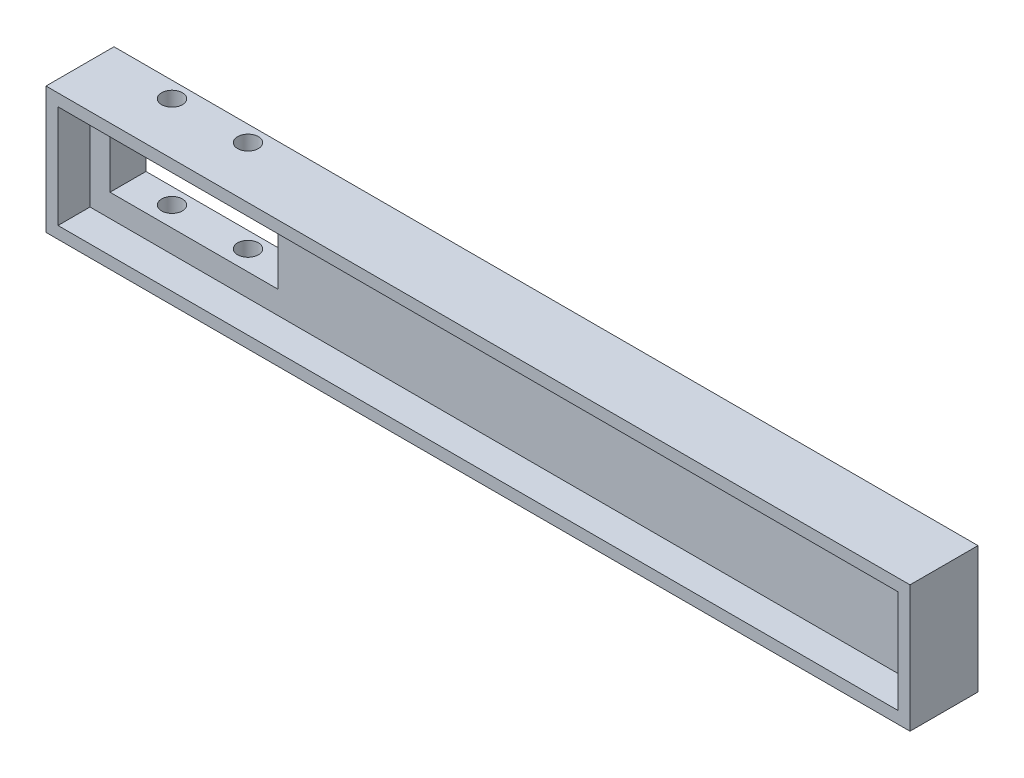
SolidWorks part; units mm, degrees
ref_plane "Plano frontal" through (0, 0, 0) normal (0, 0, 1) x (1, 0, 0)
ref_plane "Plano superior" through (0, 0, 0) normal (0, 1, 0) x (1, 0, 0)
ref_plane "Plano direito" through (0, 0, 0) normal (1, 0, 0) x (0, 0, -1)
sketch "Esboço1" plane through (0, 0, 0) normal (0, 0, 1) x (1, 0, 0)
  line L0 (-81, 8.8884) -> (-81, 14.3911)
  line L1 (0.5, 16.8911) -> (-96.5, 16.8911)
  line L2 (0.5, 16.8911) -> (0.5, 4.0411)
  line L3 (0.5, 4.0411) -> (-94.5, 4.0411)
  line L4 (-102, 14.3911) -> (-81, 14.3911)
  line L5 (0, 16.3911) -> (-97, 16.3911)
  line L6 (0, 16.3911) -> (0, 4.5411)
  line L7 (0, 4.5411) -> (-95, 4.5411)
  line L8 (-106, 2.5411) -> (-93, 2.5411)
  line L9 (2, 18.3911) -> (-95, 18.3911)
  line L10 (2, 18.3911) -> (2, 2.5411)
  line L11 (2, 2.5411) -> (-93, 2.5411)
  line L12 (-106, 18.3911) -> (-106, 2.5411)
  line L13 (-106, 18.3911) -> (-95, 18.3911)
  line L14 (-104, 4.5411) -> (-95, 4.5411)
  line L15 (-104, 16.3911) -> (-104, 4.5411)
  line L16 (-104, 16.3911) -> (-97, 16.3911)
  line L17 (-104.5, 4.0411) -> (-94.5, 4.0411)
  line L18 (-104.5, 16.8911) -> (-104.5, 4.0411)
  line L19 (-104.5, 16.8911) -> (-96.5, 16.8911)
  line L20 (-102, 14.3911) -> (-102, 6.8911)
  line L21 (-102, 6.8911) -> (-81, 6.8911)
  line L22 (-81, 6.8911) -> (-81, 8.8884)
  dimension "D1" = 11
  dimension "D2" = 2
  dimension "D3" = 0.5
  dimension "D4" = 8
  dimension "D5" = 0.5
  dimension "D6" = 7
  dimension "D7" = 2
  dimension "D8" = 2
  dimension "D9" = 97
  dimension "D10" = 97
  dimension "D11" = 97
  dimension "D12" = 7.5
  dimension "D13" = 2
  dimension "D14" = 2
extrude "Ressalto-extrusão1" add sketch "Esboço1" along normal blind 5 and the other way blind 3.5 contours L13 L12 L8 L11 L10 L9 L18 L19 L1 L2 L3 L17 region at (-104.9084, 10.4661, 0)
extrude "Ressalto-extrusão2" add sketch "Esboço1<3>" against normal blind 3.5 contours L19 L18 L17 L3 L2 L1 L15 L16 L5 L6 L7 L14 | L16 L15 L14 L7 L6 L5 region at (0.3942, 10.4661, 0) region at (-46.2123, 10.4405, 0)
sketch "Esboço1<3>" plane through (0, 0, 0) normal (0, 0, 1) x (1, 0, 0) same geometry as "Esboço1"
sketch "Esboço2" plane through (0, 18.3911, -18.3911) normal (0, -1, 0) x (1, 0, 0)
  line L1 (-106, 14.8911) -> (-106, 18.3911)
  line L2 (-106, 14.8911) -> (-106, 23.3911) construction
  circle A0 centre (-96.75, 16.8911) radius 1.3
  circle A1 centre (-87.25, 16.8911) radius 1.3
  dimension "D2" = 2.6
  dimension "D3" = 2.6
  dimension "D1" = 1.5
  dimension "D4" = 9.25
  dimension "D5" = 9.5
extrude "Ressalto-extrusão3" add sketch "Esboço1<4>" along normal blind 1 contours L19 L18 L17 L3 L2 L1 L15 L16 L5 L6 L7 L14 | L16 L15 L14 L7 L6 L5 region at (0.3942, 10.4661, 0) region at (-46.2123, 10.4405, 0)
sketch "Esboço1<4>" plane through (0, 0, 0) normal (0, 0, 1) x (1, 0, 0) same geometry as "Esboço1"
extrude "Corte-extrusão2" cut sketch "Esboço2" along normal through all contours A0 | A1 region at (-96.75, 18.3911, -1.5) region at (-87.25, 18.3911, -1.5)
